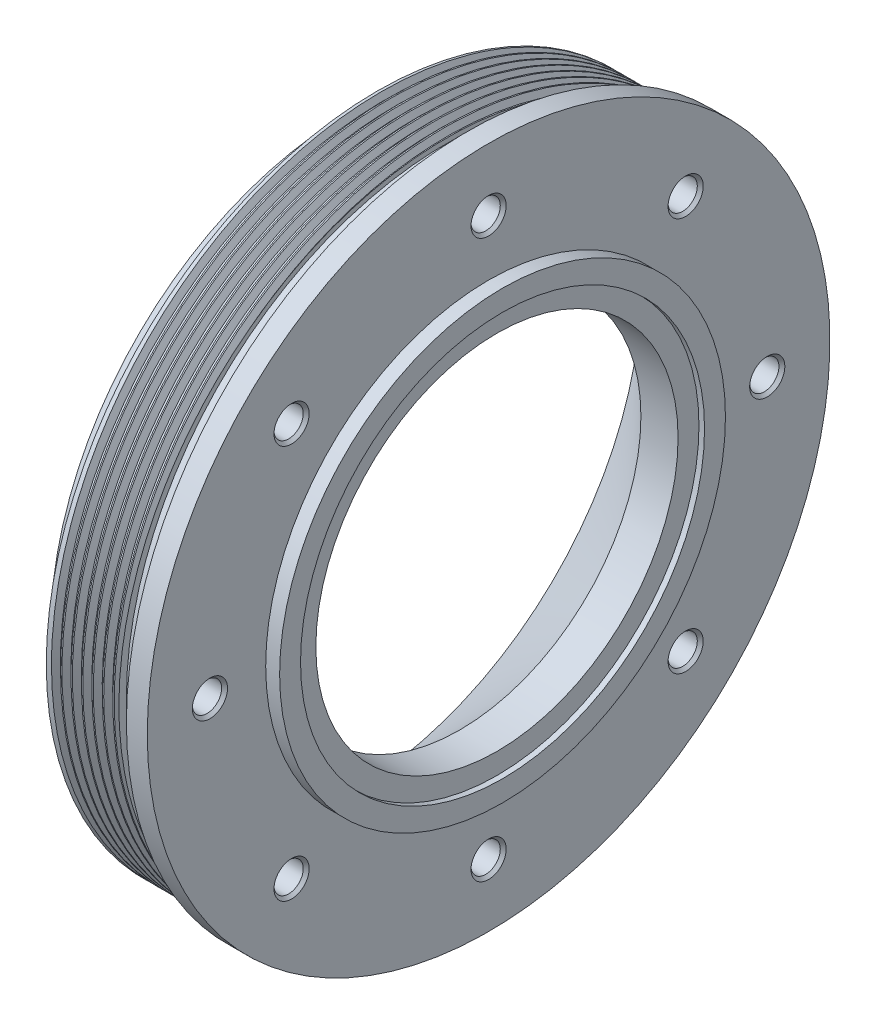
SolidWorks part; units mm, degrees
material "Copper"
ref_plane "Ebene vorne" through (0, 0, 0) normal (0, 0, 1) x (1, 0, 0)
ref_plane "Ebene oben" through (0, 0, 0) normal (0, 1, 0) x (1, 0, 0)
ref_plane "Ebene rechts" through (0, 0, 0) normal (1, 0, 0) x (0, 0, -1)
sketch "Sketch1" plane through (0, 0, 0) normal (0, 0, 1) x (1, 0, 0)
  line L0 (0, 0) -> (151.1184, 0) construction
  line L1 (0, 42.865) -> (0, 41.865)
  line L2 (0, 41.865) -> (15.865, 26)
  line L3 (15.865, 26) -> (21.2, 26)
  line L4 (21.2, 26) -> (21.2, 29)
  line L5 (21.2, 29) -> (22, 29)
  line L6 (22, 29) -> (22, 32)
  line L7 (0, 42.865) -> (4, 42.865)
  line L8 (4, 42.865) -> (4, 47.5)
  line L9 (4, 47.5) -> (14, 47.5)
  line L10 (14, 47.5) -> (14, 46)
  line L11 (14, 46) -> (17, 46)
  line L12 (17, 46) -> (17, 49)
  line L13 (17, 49) -> (20, 49)
  line L14 (20, 49) -> (20, 32)
  line L15 (20, 32) -> (22, 32)
  point P19 (17, 47.5)
  dimension "D1" = 47.5
  dimension "D2" = 1.5
  dimension "D3" = 3
  dimension "D4" = 10
  dimension "D5" = 4
  dimension "D6" = 1
  dimension "D7" = 45
  dimension "D8" = 85.73
  dimension "D9" = 98
  dimension "D10" = 3
  dimension "D11" = 32
  dimension "D12" = 3
  dimension "D13" = 26
  dimension "D14" = 0.8
  dimension "D15" = 2
revolve "Revolve1" add sketch "Sketch1" angle 360 about L0
hole_wizard "M5 Tapped Hole1" positions "Sketch2" profile "Sketch3" tap size "M5" standard "DIN"
sketch "Sketch2" plane through (20, 0, 0) normal (1, 0, 0) x (0, 0, -1)
  line L0 (0, 0) -> (40, 0) construction
  point P0 (40, 0)
  dimension "D1" = 40
sketch "Sketch3" plane through (20, 0, -40) normal (0, 1, 0) x (0, 0, -1)
  line L0 (0, 0) -> (0, 11.2618)
  line L1 (0, 11.2618) -> (2.1, 10)
  line L2 (2.1, 10) -> (2.1, 0.425)
  line L3 (2.1, 0.425) -> (2.525, 0)
  line L5 (2.525, 0) -> (0, 0)
  line L6 (-2.1, 0.425) -> (-2.525, 0) construction
  line L10 (0, 11.2618) -> (-2.1, 10) construction
  line L11 (0, -6.35) -> (0, 107.95) construction
  dimension "Tap Drill Dia." = 4.2
  dimension "Tap Drill Depth" = 10
  dimension "Near C'Sink Dia." = 5.05
  dimension "Near C'Sink Angle" = 90
  dimension "Drill Angle" = 118
cosmetic thread "Hole Thread1" parameters "D1"=6, "D2"=5
pattern_circular "CirPattern1" count 8 over 360 about axis through (0, 0, 0) along (-1, 0, 0) of "M5 Tapped Hole1"
cosmetic thread "Hole Thread2" parameters "D1"=6, "D2"=5
cosmetic thread "Hole Thread3" parameters "D1"=6, "D2"=5
cosmetic thread "Hole Thread4" parameters "D1"=6, "D2"=5
cosmetic thread "Hole Thread5" parameters "D1"=6, "D2"=5
cosmetic thread "Hole Thread6" parameters "D1"=6, "D2"=5
cosmetic thread "Hole Thread7" parameters "D1"=6, "D2"=5
cosmetic thread "Hole Thread8" parameters "D1"=6, "D2"=5
thread "Thread1" pitch 1.5 method cut profile "Thread Profile1" start angle 0, offset 0, length 0, pitch 1.5, diameter 95
ref_plane "Plane1" through (4, 0, -47.5) normal (0, -1, 0) x (0, 0, -1)
sketch "Thread Profile1" plane through (4, 0, -47.5) normal (0, -1, 0) x (0, 0, -1)
  line L0 (0, 0) -> (0, 1.5) construction
  line L11 (0, 0) -> (0, 1.3125)
  line L12 (0, 1.3125) -> (-0.8119, 0.8437)
  line L13 (-0.8119, 0.8437) -> (-0.8119, 0.4687)
  line L15 (-0.8119, 0.4687) -> (0, 0)
  line L17 (-0.8119, 0.6562) -> (0, 0.6562) construction
  point P2 (0, 0)
  dimension "Pitch" = 1.5
  dimension "Profile_Angle" = 60
  dimension "Profile_Land" = 0.375
  dimension "Profile_Height" = 0.8119
